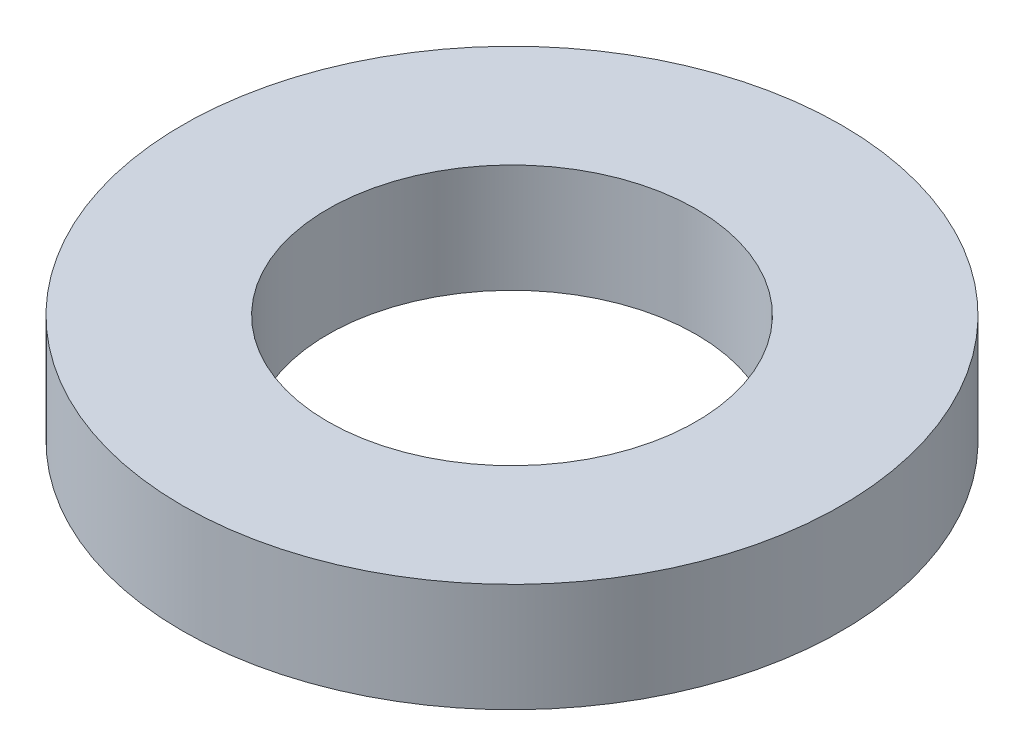
SolidWorks part; units mm, degrees
ref_plane "Front Plane" through (0, 0, 0) normal (0, 0, 1) x (1, 0, 0)
ref_plane "Top Plane" through (0, 0, 0) normal (0, 1, 0) x (1, 0, 0)
ref_plane "Right Plane" through (0, 0, 0) normal (1, 0, 0) x (0, 0, -1)
sketch "Sketch1" plane through (0, 0, 0) normal (0, 1, 0) x (1, 0, 0)
  circle A0 centre (0, 0) radius 85
  dimension "FLANGE_OD" = 170
extrude "Boss-Extrude1" add sketch "Sketch1" along normal blind 28
sketch "Sketch2" plane through (0, 0, 0) normal (0, 1, 0) x (1, 0, 0)
  circle A0 centre (0, 0) radius 47.5
  dimension "BORE_D" = 95
extrude "Cut-Extrude1" cut sketch "Sketch2" along normal through all
sketch "Sketch3" plane through (0, 28, 0) normal (0, 1, 0) x (1, 0, 0)
  circle A0 centre (0, 0) radius 34.0653 construction
  circle A1 centre (-34.0653, 0) radius 5.7856
  dimension "BOLT_D" = 11.5712
  dimension "BOLT_PCD" = 68.1307
extrude "Cut-Extrude2" cut sketch "Sketch3" against normal blind 22.4982 rebuild error yes
pattern_circular "CirPattern1" count 8 over 360 rebuild error yes
